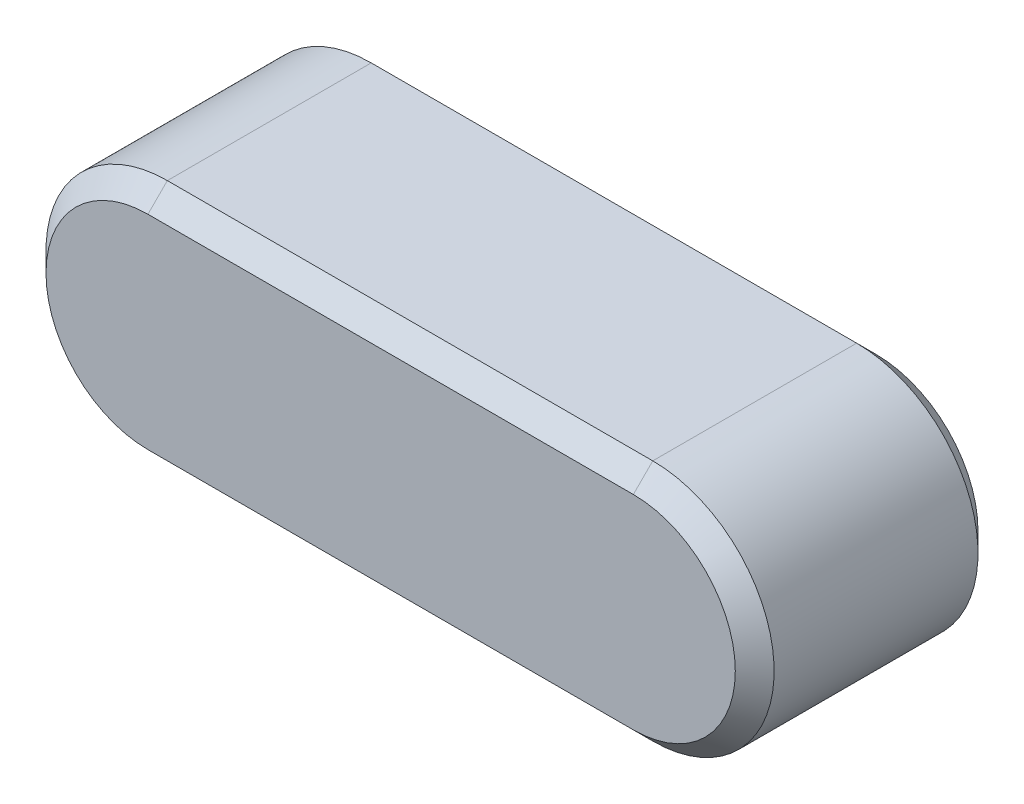
SolidWorks part; units mm, degrees
ref_plane "Front" through (0, 0, 0) normal (0, 0, 1) x (1, 0, 0)
ref_plane "Top" through (0, 0, 0) normal (0, 1, 0) x (1, 0, 0)
ref_plane "Right" through (0, 0, 0) normal (1, 0, 0) x (0, 0, -1)
sketch "Sketch1" plane through (0, 0, 0) normal (0, 0, 1) x (1, 0, 0)
  line L0 (0, 1) -> (-4, 1)
  line L1 (-4, -1) -> (0, -1)
  arc A0 (-4, 1) -> (-4, -1) centre (-4, 0) ccw
  arc A1 (0, -1) -> (0, 1) centre (0, 0) ccw
  dimension "b" = 2
  dimension "l" = 6
extrude "Extrude1" add sketch "Sketch1" along normal blind 2
sketch "Sketch3" plane through (0, 0, 0) normal (0, 0, 1) x (1, 0, 0)
  line L0 (-4, -1) -> (0, -1) construction
  line L1 (-4, -1) -> (1, -1)
  line L3 (-4, 1) -> (1, 1)
  line L4 (1, -1) -> (1, 1)
  arc A1 (-4, 1) -> (-4, -1) centre (-4, 0) ccw
  arc A2 (0, -1) -> (0, 1) centre (0, 0) ccw construction
  arc A3 (-4, 1) -> (-4, -1) centre (-4, 0) ccw construction
extrude "Extrude2" [suppressed] add sketch "Sketch3" along normal blind 2
chamfer "Chamfer1" distance 0.16 angle 45 8 edges at (-2, 1, 0) (-2, -1, 0) (-2, 1, 2) (-2, -1, 2) (-5, 0, 0) (-5, 0, 2) (1, 0, 0) (1, 0, 2)
equation "\"D1@Extrude2\" = \"h@Extrude1\""
